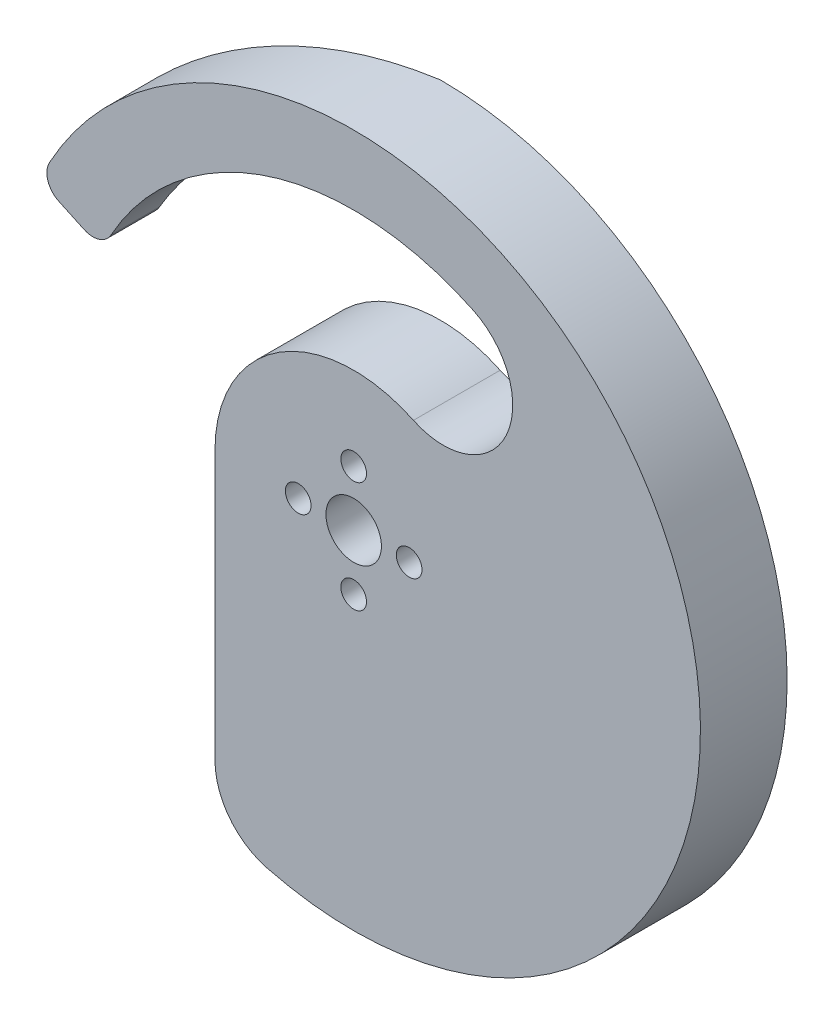
SolidWorks part; units mm, degrees
ref_plane "Front" through (0, 0, 0) normal (0, 0, 1) x (1, 0, 0)
ref_plane "Top" through (0, 0, 0) normal (0, 1, 0) x (1, 0, 0)
ref_plane "Right" through (0, 0, 0) normal (1, 0, 0) x (0, 0, -1)
sketch "Sketch1" plane through (0, 0, 0) normal (0, 0, 1) x (1, 0, 0)
  line L0 (0, 0) -> (0, 8) construction
  line L1 (0, 0) -> (-20, 0) construction
  line L3 (14.1421, 14.1421) -> (28.2843, 28.2843)
  line L4 (0, 0) -> (-45.3154, 21.1309) construction
  line L5 (-45.3154, 21.1309) -> (-36.2523, 16.9047)
  line L6 (-20, 0) -> (-20, -45.8258)
  arc A0 (-20, -45.8258) -> (-45.3154, 21.1309) centre (0, 0) ccw
  circle A1 centre (0, 0) radius 4
  circle A2 centre (0, 8) radius 1.85
  circle A3 centre (8, 0) radius 1.85
  circle A4 centre (0, -8) radius 1.85
  circle A5 centre (-8, 0) radius 1.85
  arc A6 (-20, 0) -> (14.1421, 14.1421) centre (0, 0) cw
  arc A7 (28.2843, 28.2843) -> (-36.2523, 16.9047) centre (0, 0) ccw
  point P15 (0, 0)
  dimension "D1" = 100
  dimension "D2" = 8
  dimension "D4" = 3.7
  dimension "D7" = 25
  dimension "D3" = 8
  dimension "D8" = 40
  dimension "D5" = 4
extrude "Boss-Extrude1" add sketch "Sketch1" along normal blind 12.5
fillet "Fillet1" radius 10 2 edges at (28.2843, 28.2843, 6.25) (14.1421, 14.1421, 6.25)
fillet "Fillet2" radius 3 2 edges at (-36.2523, 16.9047, 6.25) (-45.3154, 21.1309, 6.25)
fillet "Fillet3" radius 10 1 edges at (-20, -45.8258, 6.25)
ref_axis "Axis1" through (0, 50, 0) along (0, -1, 0)
ref_plane "Plane1" through (0, 0, 0) normal (-0.1564, 0, -0.9877) x (0, -1, 0)
sketch "Sketch3" plane through (0, 0, 0) normal (-0.1564, 0, -0.9877) x (0, -1, 0)
  line L0 (-59.4124, 3.0597) -> (-37.4566, -8.5417)
  line L1 (-59.4124, 3.0597) -> (-32.3558, 54.2649)
  line L3 (-32.3558, 54.2649) -> (-10.4, 42.6635)
  line L4 (-37.4566, -8.5417) -> (-10.4, 42.6635)
extrude "Cut-Extrude1" cut sketch "Sketch3" along normal blind 20
